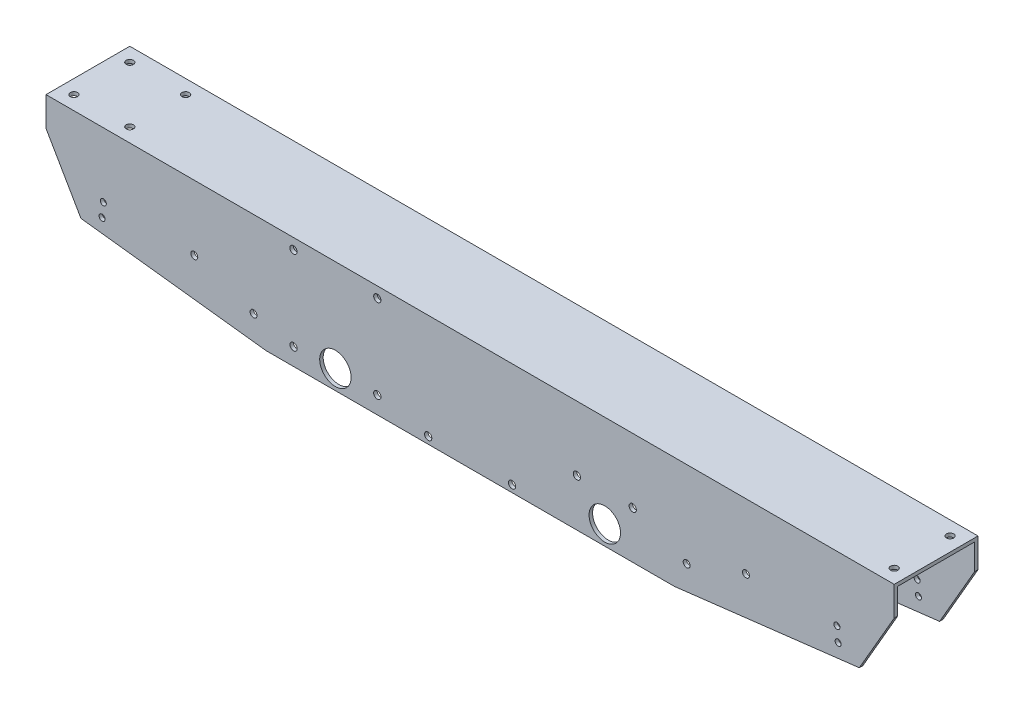
SolidWorks part; units mm, degrees
ref_plane "Front Plane" through (0, 0, 0) normal (0, 0, 1) x (1, 0, 0)
ref_plane "Top Plane" through (0, 0, 0) normal (0, 1, 0) x (1, 0, 0)
ref_plane "Right Plane" through (0, 0, 0) normal (1, 0, 0) x (0, 0, -1)
sketch "Sketch1" plane through (0, 0, 0) normal (1, 0, 0) x (0, 0, -1)
  line L0 (-34.925, 47.625) -> (-34.925, -47.625) construction
  line L1 (-38.1, 50.8) -> (38.1, 50.8)
  line L2 (-38.1, 50.8) -> (-38.1, -50.8)
  line L3 (-38.1, -50.8) -> (-34.925, -50.8)
  line L4 (38.1, 50.8) -> (38.1, -50.8)
  line L5 (-38.1, 50.8) -> (38.1, -50.8) construction
  line L6 (-38.1, -50.8) -> (38.1, 50.8) construction
  line L7 (34.925, 47.625) -> (34.925, -50.8)
  line L8 (-34.925, 47.625) -> (34.925, 47.625)
  line L9 (-34.925, 47.625) -> (-34.925, -50.8)
  line L10 (-34.925, -47.625) -> (34.925, -47.625) construction
  line L11 (34.925, 47.625) -> (34.925, -47.625) construction
  line L12 (-38.1, -50.8) -> (38.1, -50.8) construction
  line L13 (38.1, -50.8) -> (34.925, -50.8)
  point P0 (0, 0)
  dimension "D1" = 76.2
  dimension "D2" = 101.6
  dimension "D3" = 3.175
extrude "Boss-Extrude1" add sketch "Sketch1" along normal mid plane 771.4115
sketch "Sketch2" plane through (0, 0, 38.1) normal (0, 0, 1) x (1, 0, 0)
  line L0 (-405.1565, -33.274) -> (428.5144, -33.274) construction
  line L1 (385.7058, -50.8) -> (-385.7058, -50.8) construction
  line L3 (-122.5, 124.7315) -> (-122.5, -108.8261) construction
  line L4 (-122.5, 124.7315) -> (-122.5, -108.8261) construction
  line L7 (0, 107.4469) -> (0, -99.4956) construction
  line L9 (0, -41.91) -> (0, 41.91) construction
  line L13 (0, 50.8) -> (0, -55.872) construction
  line L14 (385.7058, 50.8) -> (-385.7058, 50.8) construction
  circle A0 centre (-333.5772, -7.874) radius 2.75
  circle A1 centre (334.7203, -20.574) radius 2.75
  circle A2 centre (333.5772, -7.874) radius 2.75
  circle A4 centre (-160.6, -35.12) radius 3.302
  circle A5 centre (-160.6, 41.08) radius 3.302
  circle A6 centre (-122.5, -33.274) radius 14.2875
  circle A7 centre (-334.7203, -20.574) radius 2.75
  circle A8 centre (-84.4, 41.08) radius 3.302
  circle A9 centre (-84.4, -35.12) radius 3.302
  circle A13 centre (122.5, -33.274) radius 14.2875
  point P16 (-122.5, -33.274)
  dimension "D1" = 17.526
  dimension "D2" = 212.6
  dimension "D3" = 212.6
  dimension "D4" = 122.5
  dimension "D7" = 25.4
  dimension "D8" = 12.7
  dimension "D9" = 76.2
  dimension "D10" = 76.2
  dimension "D11" = 76.2
  dimension "D12" = 6.604
  dimension "D13" = 15.68
  dimension "D14" = 38.1
extrude "Axles" cut sketch "Sketch2" against normal blind 141.732
sketch "Flanigan mounting holes" plane through (0, 0, 38.1) normal (0, 0, 1) x (1, 0, 0)
  line L0 (122.5, 79.5654) -> (122.5, -33.274) construction
  line L2 (97.1, 9.7703) -> (97.1, -58.1396) construction
  line L3 (385.7058, -50.8) -> (-385.7058, -50.8) construction
  line L4 (147.9, 11.4068) -> (147.9, -61.409) construction
  line L5 (147.9, -44.45) -> (97.1, -44.45) construction
  circle A1 centre (97.1, -7.87) radius 3.3
  circle A3 centre (147.9, -7.87) radius 3.3
  circle A5 centre (122.5, -33.274) radius 14.2875 construction
  point P4 (147.9, -7.87)
  point P5 (97.1, -7.87)
  point P6 (122.5, 14.36)
  dimension "D6" = 42.93
  dimension "D7" = 42.93
  dimension "D8" = 6.35
  dimension "D1" = 0
  dimension "D2" = 25.4
  dimension "D3" = 25.4
  dimension "D4" = 22.23
extrude "Flanigan mounting holes extrusion" cut sketch "Flanigan mounting holes" against normal through all
sketch "Sketch16" plane through (0, 0, 38.1) normal (0, 0, 1) x (1, 0, 0)
  line L0 (-353.9515, -30.8) -> (-185.7058, -50.8)
  line L1 (-385.7058, 50.8) -> (-385.7058, -50.8) construction
  line L2 (-385.7058, 24.2) -> (-353.9515, -30.8)
  line L3 (385.7058, -50.8) -> (-385.7058, -50.8) construction
  line L4 (-385.7058, 24.2) -> (-385.7058, -50.8)
  line L5 (-385.7058, -50.8) -> (-185.7058, -50.8)
  line L6 (0, 50.8) -> (0, -65.171) construction
  line L7 (0, -41.91) -> (0, 41.91) construction
  line L8 (0, 74.5999) -> (0, -74.6877) construction
  line L9 (385.7058, -50.8) -> (185.7058, -50.8)
  line L10 (385.7058, 24.2) -> (385.7058, -50.8)
  line L11 (385.7058, 24.2) -> (353.9515, -30.8)
  line L12 (353.9515, -30.8) -> (185.7058, -50.8)
  dimension "D1" = 60
extrude "Beveled ends" cut sketch "Sketch16" against normal blind 101.6
sketch "Sketch32" plane through (0, 0, -38.1) normal (0, 0, -1) x (-1, 0, 0)
  line L0 (0, 41.91) -> (0, -41.91) construction
  line L1 (-185.7058, -50.8) -> (185.7058, -50.8) construction
  line L3 (0, 54.6658) -> (0, -55.1985) construction
  circle A0 centre (-38.1, -44.45) radius 3.3
  circle A1 centre (38.1, -44.45) radius 3.3
  point P8 (38.1, -44.45)
  dimension "D1" = 6.6
  dimension "D3" = 6.35
  dimension "D2" = 38.1
extrude "Belt shield holes" cut sketch "Sketch32" against normal through all
sketch "Sketch37" plane through (0, 50.8, 0) normal (0, 1, 0) x (1, 0, 0)
  line L0 (385.7058, 38.1) -> (-385.7058, 38.1) construction
  line L1 (385.7058, 38.1) -> (385.7058, -38.1) construction
  line L2 (385.7058, -38.1) -> (-385.7058, -38.1) construction
  line L3 (-385.7058, 38.1) -> (-385.7058, -38.1) construction
  circle A0 centre (373.0058, 25.4) radius 3.3
  circle A1 centre (373.0058, -25.4) radius 3.3
  circle A2 centre (-322.2058, 25.4) radius 3.3
  circle A3 centre (-322.2058, -25.4) radius 3.3
  circle A4 centre (-373.0058, 25.4) radius 3.3
  circle A5 centre (-373.0058, -25.4) radius 3.3
  dimension "D1" = 6.6
  dimension "D2" = 12.7
  dimension "D3" = 12.7
  dimension "D4" = 63.5
  dimension "D6" = 12.7
  dimension "D10" = 12.7
extrude "Top holes" cut sketch "Sketch37" against normal through all
sketch "Sketch38" plane through (0, 0, 38.1) normal (0, 0, 1) x (1, 0, 0)
  line L0 (385.7058, 50.8) -> (-385.7058, 50.8) construction
  line L1 (0, 50.8) -> (0, -50.6681) construction
  line L2 (0, -41.91) -> (0, 41.91) construction
  circle A0 centre (-250.8318, -8.382) radius 3.15
  circle A1 centre (-196.9247, -27.3598) radius 3.15
  circle A2 centre (196.9247, -27.3598) radius 3.15
  circle A3 centre (250.8318, -8.382) radius 3.15
  dimension "D1" = 59.182
  dimension "D2" = 134.874
  dimension "D3" = 6.3
  dimension "D4" = 57.15
  dimension "D6" = 6.3
  dimension "D5" = 188.781
extrude "Cut-Extrude1" cut sketch "Sketch38" against normal through all
